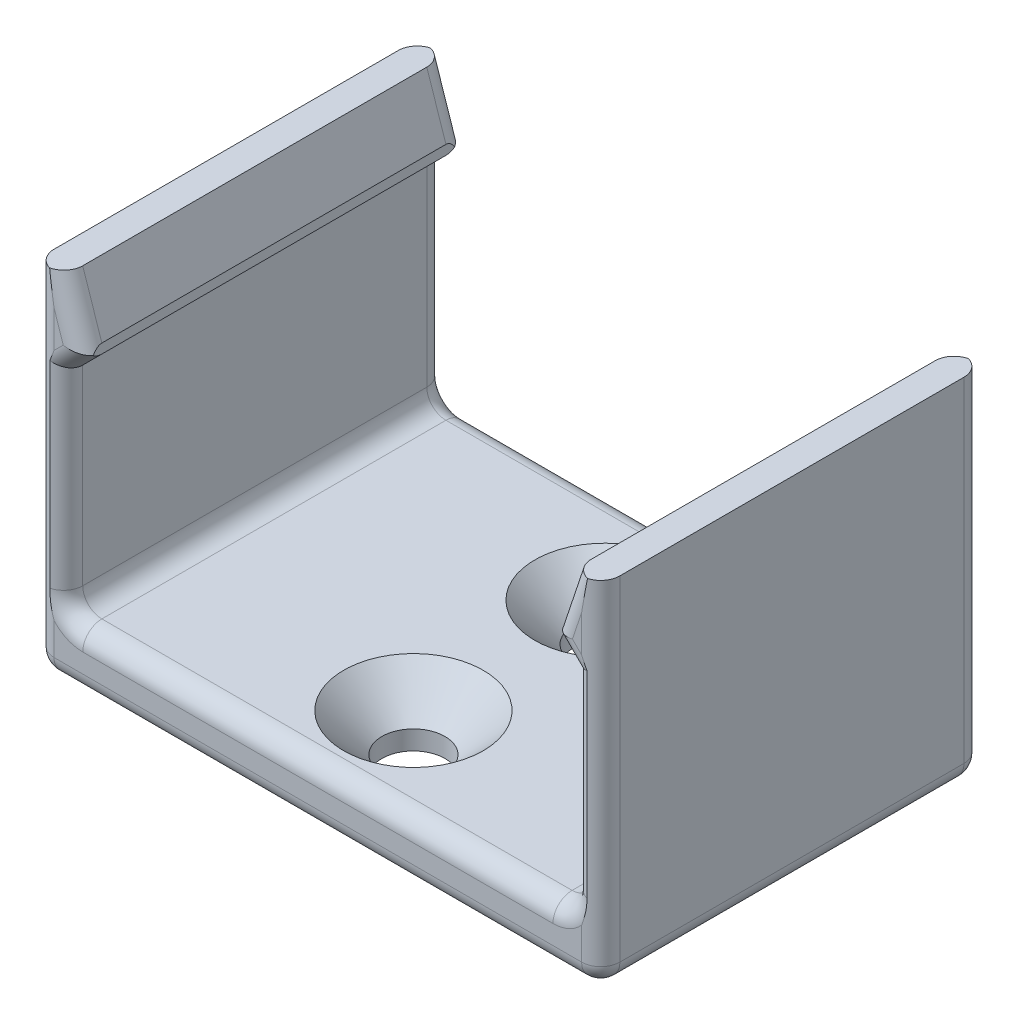
SolidWorks part; units mm, degrees
ref_plane "Front Plane" through (0, 0, 0) normal (0, 0, 1) x (1, 0, 0)
ref_plane "Top Plane" through (0, 0, 0) normal (0, 1, 0) x (1, 0, 0)
ref_plane "Right Plane" through (0, 0, 0) normal (1, 0, 0) x (0, 0, -1)
sketch "Sketch1" plane through (0, 0, 0) normal (0, 0, 1) x (1, 0, 0)
  line L0 (0, 0) -> (0, 6.5078) construction
  line L1 (0, 0) -> (-12.3, 0)
  line L2 (-13.3, 1) -> (-13.3, 11)
  line L3 (-13.3, 11) -> (-12.3, 12)
  line L4 (-12.3, 12) -> (-12.3, 12.5)
  line L5 (-12.3, 12.5) -> (-13.3, 15.5)
  line L6 (-13.3, 15.5) -> (-14.8, 15.5)
  line L7 (-14.8, 15.5) -> (-14.8, -3)
  line L8 (-14.8, -3) -> (0, -3)
  line L9 (0, 0) -> (0, -3)
  arc A0 (-12.3, 0) -> (-13.3, 1) centre (-12.3, 1) cw
  point P12 (-13.3, 0)
  dimension "D9" = 1
  dimension "D1" = 26.6
  dimension "D2" = 1
  dimension "D3" = 1
  dimension "D4" = 3
  dimension "D5" = 1.5
  dimension "D6" = 3
  dimension "D7" = 0.5
  dimension "D8" = 11
extrude "Boss-Extrude1" add sketch "Sketch1" along normal blind 20
mirror "Mirror1" about plane through (0, 0, 20) normal (-1, 0, 0) of "Boss-Extrude1"
sketch "Sketch2" plane through (0, 0, 0) normal (0, 1, 0) x (1, 0, 0)
  line L0 (0, 0) -> (0, -20) construction
  line L1 (12.3, 0) -> (-12.3, 0) construction
  line L2 (12.3, -20) -> (-12.3, -20) construction
  circle A0 centre (0, -5) radius 1.65
  circle A1 centre (0, -15) radius 1.65
  dimension "D1" = 10
  dimension "D2" = 3.3
  dimension "D3" = 5
extrude "Cut-Extrude1" cut sketch "Sketch2" against normal blind 20
fillet "Fillet2" radius 1 26 edges at (-13.0071, 0.2929, 0) (-13.3, 6, 0) (-12.8, 11.5, 0) (-12.8, 14, 0) (-14.8, 6.25, 0) (0, -3, 0) (14.8, 6.25, 0) (12.8, 14, 0) (12.8, 11.5, 0) (13.3, 6, 0) (13.0071, 0.2929, 0) (0, 0, 0) (-14.8, 6.25, 20) (-12.8, 14, 20) (-12.8, 11.5, 20) (-13.3, 6, 20) (-13.0071, 0.2929, 20) (0, 0, 20) (13.0071, 0.2929, 20) (13.3, 6, 20) (12.8, 11.5, 20) (12.8, 14, 20) (14.8, 6.25, 20) (0, -3, 20) (14.8, -3, 10) (-14.8, -3, 10)
chamfer "Chamfer1" distance 2 angle 45 2 edges at (-1.65, 0, 5) (-1.65, 0, 15)
